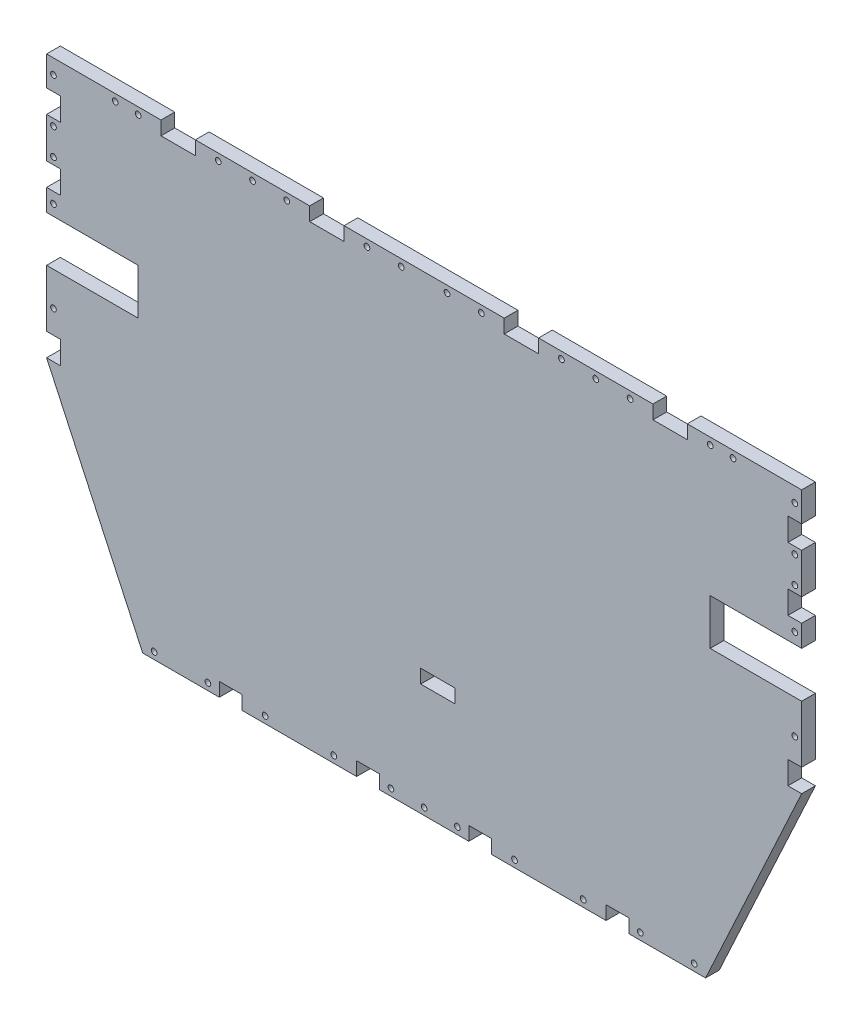
SolidWorks part; units mm, degrees
ref_plane "Plan de face" through (0, 0, 0) normal (0, 0, 1) x (1, 0, 0)
ref_plane "Plan de dessus" through (0, 0, 0) normal (0, 1, 0) x (1, 0, 0)
ref_plane "Plan de droite" through (0, 0, 0) normal (1, 0, 0) x (0, 0, -1)
sketch "Esquisse1" plane through (0, 0, 0) normal (0, 0, 1) x (1, 0, 0)
  line L0 (0, 124.9429) -> (0, -204.46) construction
  line L1 (-165, 96.73) -> (165, 96.73)
  line L2 (165, 96.73) -> (165, -18.27)
  line L3 (165, -18.27) -> (123, -109.0224)
  line L4 (123, -109.0224) -> (-123, -109.0224)
  line L5 (-211.9802, 0) -> (248.5953, 0) construction
  line L6 (-123, -109.0224) -> (-165, -18.27)
  line L7 (-165, -18.27) -> (-165, 96.73)
  dimension "D2" = 165
  dimension "D3" = 330
  dimension "D4" = 100
  dimension "D5" = 115
  dimension "D6" = 100
  dimension "D7" = 246
  dimension "D8" = 205.7524
  dimension "D9" = 96.73
  dimension "D10" = 115
extrude "Boss.-Extru.1" add sketch "Esquisse1" along normal blind 6
sketch "Esquisse3" plane through (0, 0, 0) normal (0, 0, -1) x (-1, 0, 0)
  line L0 (165, 96.73) -> (165, -18.27) construction
  line L1 (165, -18.27) -> (159, -18.27)
  line L2 (165, -18.27) -> (165, -8.27)
  line L3 (165, -8.27) -> (159, -8.27)
  line L4 (159, -18.27) -> (159, -8.27)
  line L5 (123, -109.0224) -> (-123, -109.0224) construction
  line L6 (165, 73.8526) -> (159, 73.8526)
  line L7 (165, 73.8526) -> (165, 83.8526)
  line L8 (165, 83.8526) -> (159, 83.8526)
  line L9 (159, 73.8526) -> (159, 83.8526)
  line L10 (29.5, -109.0224) -> (19.5, -109.0224)
  line L11 (29.5, -109.0224) -> (29.5, -103.0224)
  line L12 (29.5, -103.0224) -> (19.5, -103.0224)
  line L13 (19.5, -109.0224) -> (19.5, -103.0224)
  line L14 (-159, 46.23) -> (-159, 56.23)
  line L15 (0, -209.4812) -> (0, 177.1799) construction
  line L16 (123, -109.0224) -> (-123, -109.0224) construction
  line L17 (-165, 56.23) -> (-159, 56.23)
  line L18 (-19.5, -109.0224) -> (-19.5, -103.0224)
  line L19 (-29.5, -103.0224) -> (-19.5, -103.0224)
  line L20 (-29.5, -109.0224) -> (-29.5, -103.0224)
  line L21 (-29.5, -109.0224) -> (-19.5, -109.0224)
  line L22 (-159, 73.8526) -> (-159, 83.8526)
  line L23 (-165, 83.8526) -> (-159, 83.8526)
  line L24 (-165, 73.8526) -> (-165, 83.8526)
  line L25 (-165, 73.8526) -> (-159, 73.8526)
  line L26 (-159, -18.27) -> (-159, -8.27)
  line L27 (-165, -8.27) -> (-159, -8.27)
  line L28 (-165, -18.27) -> (-165, -8.27)
  line L29 (-165, -18.27) -> (-159, -18.27)
  line L30 (-165, 96.73) -> (165, 96.73) construction
  line L31 (115, 96.73) -> (100, 96.73)
  line L32 (115, 96.73) -> (115, 90.73)
  line L33 (115, 90.73) -> (100, 90.73)
  line L34 (100, 96.73) -> (100, 90.73)
  line L35 (-35, 96.73) -> (-35, 90.73)
  line L36 (50, 96.73) -> (35, 96.73)
  line L37 (50, 96.73) -> (50, 90.73)
  line L38 (50, 90.73) -> (35, 90.73)
  line L39 (35, 96.73) -> (35, 90.73)
  line L40 (-50, 90.73) -> (-35, 90.73)
  line L41 (-50, 96.73) -> (-50, 90.73)
  line L42 (-50, 96.73) -> (-35, 96.73)
  line L43 (-100, 96.73) -> (-100, 90.73)
  line L44 (-115, 90.73) -> (-100, 90.73)
  line L45 (-115, 96.73) -> (-115, 90.73)
  line L46 (-115, 96.73) -> (-100, 96.73)
  line L47 (-165, 46.23) -> (-165, 56.23)
  line L48 (79.5, -109.0224) -> (89.5, -109.0224)
  line L49 (79.5, -109.0224) -> (79.5, -103.0224)
  line L50 (79.5, -103.0224) -> (89.5, -103.0224)
  line L51 (89.5, -109.0224) -> (89.5, -103.0224)
  line L52 (165, 46.23) -> (159, 46.23)
  line L53 (165, 46.23) -> (165, 56.23)
  line L54 (165, 56.23) -> (159, 56.23)
  line L55 (159, 46.23) -> (159, 56.23)
  line L56 (-165, 46.23) -> (-159, 46.23)
  line L57 (-89.5, -109.0224) -> (-89.5, -103.0224)
  line L58 (-79.5, -103.0224) -> (-89.5, -103.0224)
  line L59 (-79.5, -109.0224) -> (-79.5, -103.0224)
  line L60 (-79.5, -109.0224) -> (-89.5, -109.0224)
  line L61 (-165, -18.27) -> (-165, 96.73) construction
  line L62 (1.5, -60.0224) -> (-13.5, -60.0224)
  line L63 (1.5, -60.0224) -> (1.5, -54.0224)
  line L64 (1.5, -54.0224) -> (-13.5, -54.0224)
  line L65 (-13.5, -60.0224) -> (-13.5, -54.0224)
  line L66 (-165, 36.73) -> (-125, 36.73)
  line L67 (-165, 36.73) -> (-165, 16.73)
  line L68 (-165, 16.73) -> (-125, 16.73)
  line L69 (-125, 36.73) -> (-125, 16.73)
  line L70 (125, 36.73) -> (125, 16.73)
  line L71 (165, 16.73) -> (125, 16.73)
  line L72 (165, 36.73) -> (165, 16.73)
  line L73 (165, 36.73) -> (125, 36.73)
  dimension "D1" = 10
  dimension "D2" = 6
  dimension "D3" = 6
  dimension "D4" = 10
  dimension "D5" = 10
  dimension "D6" = 6
  dimension "D7" = 19.5
  dimension "D9" = 12.8774
  dimension "D10" = 15
  dimension "D11" = 15
  dimension "D12" = 50
  dimension "D13" = 50
  dimension "D14" = 6
  dimension "D15" = 50
  dimension "D16" = 10
  dimension "D17" = 6
  dimension "D18" = 6
  dimension "D19" = 10
  dimension "D20" = 40.5
  dimension "D21" = 6
  dimension "D22" = 49
  dimension "D23" = 121.5
  dimension "D24" = 15
  dimension "D25" = 6
  dimension "D26" = 60
  dimension "D27" = 20
  dimension "D28" = 40
extrude "Enlèv. mat.-Extru.2" cut sketch "Esquisse3" against normal blind 6
sketch "Esquisse4" plane through (0, 0, 0) normal (0, 0, -1) x (-1, 0, 0)
  line L0 (159, 73.8526) -> (165, 73.8526) construction
  line L1 (29.5, -109.0224) -> (29.5, -103.0224) construction
  line L2 (-14.5, -106.0224) -> (156.1766, -106.0224) construction
  line L3 (123, -109.0224) -> (89.5, -109.0224) construction
  line L4 (79.5, -103.0224) -> (79.5, -109.0224) construction
  line L6 (115, 96.73) -> (165, 96.73) construction
  line L7 (19.5, -103.0224) -> (19.5, -109.0224) construction
  line L8 (165, 73.8526) -> (165, 56.23) construction
  line L9 (89.5, -109.0224) -> (89.5, -103.0224) construction
  line L10 (165, 96.73) -> (165, 83.8526) construction
  line L11 (143.8632, 93.73) -> (10, 93.73) construction
  line L12 (50, 96.73) -> (100, 96.73) construction
  line L13 (115, 90.73) -> (115, 96.73) construction
  line L14 (100, 96.73) -> (100, 90.73) construction
  line L15 (50, 90.73) -> (50, 96.73) construction
  line L16 (35, 96.73) -> (35, 90.73) construction
  line L17 (0, 142.2997) -> (0, -202.2086) construction
  line L18 (-162, -8.8123) -> (-162, 103.5881) construction
  line L19 (165, 56.23) -> (159, 56.23) construction
  line L20 (159, 46.23) -> (165, 46.23) construction
  line L21 (165, -8.27) -> (159, -8.27) construction
  line L22 (162, -8.8123) -> (162, 103.5881) construction
  line L23 (-143.8632, 93.73) -> (-10, 93.73) construction
  line L24 (14.5, -106.0224) -> (-156.1766, -106.0224) construction
  circle A0 centre (162, 1.92) radius 1.25
  circle A1 centre (69.5, -106.0224) radius 1.25
  circle A2 centre (162, 70.8526) radius 1.25
  circle A3 centre (0, -106.0224) radius 1.25
  circle A4 centre (94.5, -106.0224) radius 1.25
  circle A5 centre (162, 90.29) radius 1.25
  circle A6 centre (-162, 41.48) radius 1.25
  circle A7 centre (14.5, -106.0224) radius 1.25
  circle A8 centre (118, -106.0224) radius 1.25
  circle A9 centre (39.5, -106.0224) radius 1.25
  circle A10 centre (135, 93.73) radius 1.25
  circle A11 centre (125, 93.73) radius 1.25
  circle A12 centre (90, 93.73) radius 1.25
  circle A13 centre (75, 93.73) radius 1.25
  circle A14 centre (60, 93.73) radius 1.25
  circle A15 centre (25, 93.73) radius 1.25
  circle A16 centre (10, 93.73) radius 1.25
  circle A17 centre (-162, 59.23) radius 1.25
  circle A18 centre (-10, 93.73) radius 1.25
  circle A19 centre (-25, 93.73) radius 1.25
  circle A20 centre (-60, 93.73) radius 1.25
  circle A21 centre (-75, 93.73) radius 1.25
  circle A22 centre (-90, 93.73) radius 1.25
  circle A23 centre (-125, 93.73) radius 1.25
  circle A24 centre (-135, 93.73) radius 1.25
  circle A25 centre (-39.5, -106.0224) radius 1.25
  circle A26 centre (-118, -106.0224) radius 1.25
  circle A27 centre (-14.5, -106.0224) radius 1.25
  circle A28 centre (-162, 90.29) radius 1.25
  circle A29 centre (-94.5, -106.0224) radius 1.25
  circle A31 centre (-162, 70.8526) radius 1.25
  circle A32 centre (162, 59.23) radius 1.25
  circle A33 centre (162, 41.48) radius 1.25
  circle A34 centre (-69.5, -106.0224) radius 1.25
  circle A35 centre (-162, 1.92) radius 1.25
  dimension "D1" = 2.5
  dimension "D3" = 2.5
  dimension "D10" = 2.5
  dimension "D11" = 2.5
  dimension "D12" = 10
  dimension "D13" = 2.5
  dimension "D14" = 2.5
  dimension "D18" = 3
  dimension "D19" = 2.5
  dimension "D29" = 2.5
  dimension "D30" = 2.5
  dimension "D31" = 2.5
  dimension "D32" = 2.5
  dimension "D33" = 2.5
  dimension "D34" = 2.5
  dimension "D35" = 4.75
  dimension "D40" = 10
  dimension "D5" = 10.19
  dimension "D8" = 10
  dimension "D15" = 2.5
  dimension "D20" = 2.5
  dimension "D17" = 5
  dimension "D21" = 5
  dimension "D22" = 5
  dimension "D23" = 2.5
  dimension "D25" = 2.5
  dimension "D27" = 3
  dimension "D6" = 3
  dimension "D7" = 6.44
  dimension "D9" = 3
  dimension "D24" = 3
  dimension "D26" = 3
  dimension "D28" = 3
  dimension "D36" = 10
  dimension "D37" = 10
  dimension "D38" = 10
  dimension "D39" = 15
  dimension "D41" = 15
  dimension "D42" = 10
extrude "Enlèv. mat.-Extru.3" cut sketch "Esquisse4" against normal blind 6
